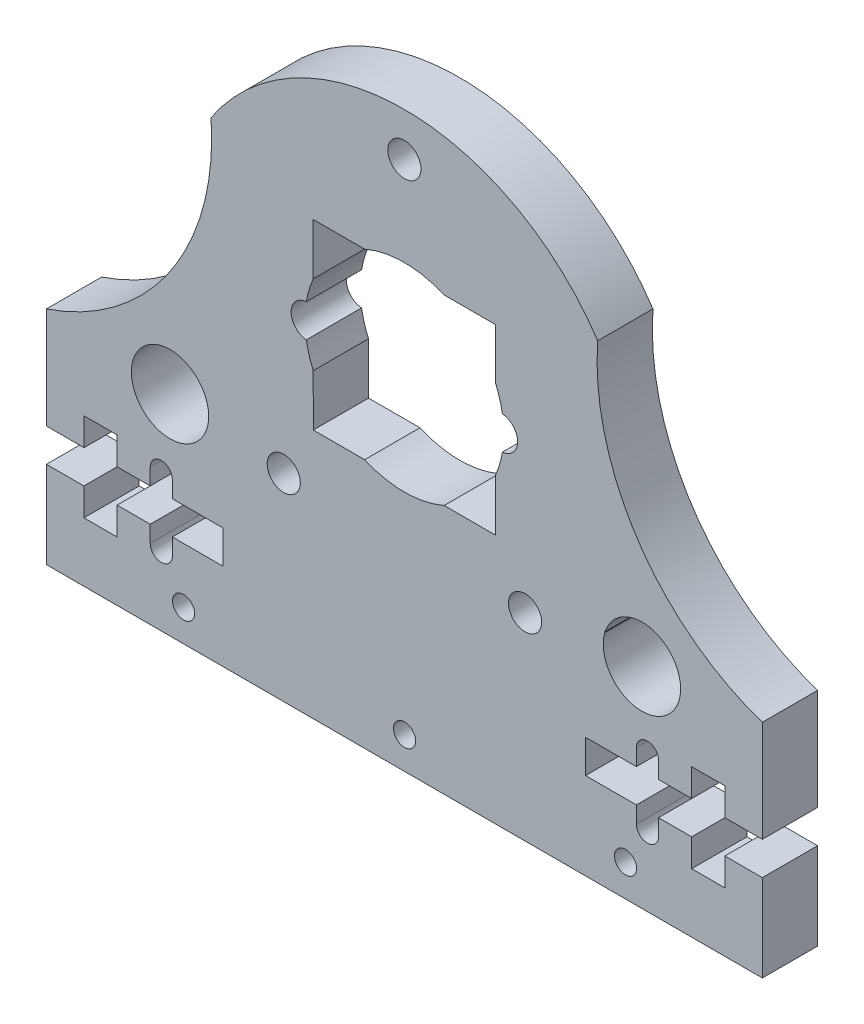
SolidWorks part; units mm, degrees
ref_plane "Front Plane" through (0, 0, 0) normal (0, 0, 1) x (1, 0, 0)
ref_plane "Top Plane" through (0, 0, 0) normal (0, 1, 0) x (1, 0, 0)
ref_plane "Right Plane" through (0, 0, 0) normal (1, 0, 0) x (0, 0, -1)
sketch "Sketch1" plane through (0, 0, 0) normal (0, 0, 1) x (1, 0, 0)
  line L0 (7.049, 19.6325) -> (17.9731, -10.4272)
  line L1 (-11.086, -20.4888) -> (10.9241, -20.4888)
  line L2 (-7.0493, 19.6315) -> (-17.9689, -10.4301)
  line L68 (-32.396, -10.8383) -> (-32.396, -30.8817)
  line L69 (-32.396, -10.8383) -> (32.396, -10.8383)
  line L70 (32.396, -10.8383) -> (32.396, -30.8817)
  line L71 (-32.396, -30.8817) -> (32.396, -30.8817)
  line L72 (-32.396, -10.8383) -> (32.396, -30.8817) construction
  line L73 (32.396, -10.8383) -> (-32.396, -30.8817) construction
  line L83 (8.2458, 8.2543) -> (3.5926, 8.2519)
  line L84 (-3.6012, 8.2481) -> (-8.2543, 8.2457)
  line L85 (-8.2543, 8.2457) -> (-8.2519, 3.5926)
  line L86 (-8.2481, -3.6012) -> (-8.2457, -8.2543)
  line L87 (-8.2457, -8.2543) -> (-3.5926, -8.2519)
  line L88 (3.6012, -8.2481) -> (8.2543, -8.2457)
  line L89 (8.2543, -8.2457) -> (8.2519, -3.5217)
  line L90 (8.2481, 3.672) -> (8.2458, 8.2543)
  arc A0 (7.049, 19.6325) -> (-7.0493, 19.6315) centre (0, 17.0709) ccw
  arc A1 (10.9241, -20.4888) -> (17.9731, -10.4272) centre (10.9241, -12.9888) ccw
  arc A2 (-17.9689, -10.4301) -> (-10.7531, -20.4888) centre (-10.9196, -12.9907) ccw
  circle A3 centre (0, 17.0709) radius 1.5
  circle A4 centre (10.9241, -12.9888) radius 1.5
  circle A5 centre (-10.9196, -12.9907) radius 1.5
  arc A6 (-28.1118, -10.8383) -> (-16.6025, -6.6683) centre (-21.209, -11.9221) cw
  arc A7 (16.6787, -6.8654) -> (28.4035, -10.8383) centre (21.5008, -11.9221) cw
  circle A8 centre (0, 0.0709) radius 17 construction
  circle A78 centre (21.5008, -11.9221) radius 3.5
  circle A79 centre (-21.209, -11.9221) radius 3.5
  arc A94 (3.5926, 8.2519) -> (-3.6012, 8.2481) centre (0, 0) ccw
  arc A95 (-8.2519, 3.5926) -> (-8.8758, 1.4902) centre (0, 0) ccw
  arc A96 (-8.8758, 1.4902) -> (-8.8742, -1.4994) centre (-8.75, -0.0045) ccw
  arc A97 (-8.8742, -1.4994) -> (-8.2481, -3.6012) centre (0, 0) ccw
  arc A98 (-3.5926, -8.2519) -> (3.6012, -8.2481) centre (0, 0) ccw
  arc A99 (8.2519, -3.5217) -> (8.8758, -1.4193) centre (0, 0.0709) ccw
  arc A100 (8.8758, -1.4193) -> (8.8742, 1.5702) centre (8.75, 0.0754) ccw
  arc A101 (8.8742, 1.5702) -> (8.2481, 3.672) centre (0, 0.0709) ccw
  point P18 (0, -20.86)
  dimension "D1" = 15
  dimension "D2" = 7
  dimension "D3" = 34
extrude "Boss-Extrude1" add sketch "Sketch1" along normal blind 5 contours A79 L69 A78 L0 A0 L2 A101 A100 A99 L89 L88 A98 L87 L86 A97 A96 A95 L85 L84 A94 L83 L90 A3 | A79 A2 L1 A1 A78 L69 A5 A4 | A79 L69 L68 L71 L70 A78 A1 L1 A2 | A79 L2 A6 L69 | A78 L69 A7 L0 region at (11.3885, 6.2108, 0) region at (22.5052, -7.7427, 0) region at (-0.0256, -23.2651, 0) region at (-22.3529, -7.7149, 0) region at (0.0494, -15.5713, 0)
sketch "Sketch2" plane through (0, 0, 5) normal (0, 0, 1) x (1, 0, 0)
  line L0 (26.0003, -21.5138) -> (24.396, -21.5138) construction
  line L1 (26.0003, -17.5138) -> (29.0003, -17.5138)
  line L2 (26.0003, -25.5138) -> (26.0003, -17.5138)
  line L3 (29.0003, -17.5138) -> (29.0003, -25.5138)
  line L4 (29.0003, -25.5138) -> (26.0003, -25.5138)
  line L5 (32.396, -23.0138) -> (16.396, -23.0138)
  line L6 (32.396, -23.0138) -> (32.396, -20.0138)
  line L7 (32.396, -20.0138) -> (16.396, -20.0138)
  line L8 (16.396, -23.0138) -> (16.396, -20.0138)
  line L9 (32.396, -23.0138) -> (16.396, -20.0138) construction
  line L10 (32.396, -20.0138) -> (16.396, -23.0138) construction
  line L11 (22.0003, -18.5138) -> (22.0003, -24.5138) construction
  line L12 (23.0003, -18.5138) -> (23.0003, -24.5138)
  line L13 (21.0003, -18.5138) -> (21.0003, -24.5138)
  line L14 (32.396, -10.8383) -> (32.396, -30.8817) construction
  arc A0 (23.0003, -18.5138) -> (21.0003, -18.5138) centre (22.0003, -18.5138) ccw
  arc A1 (21.0003, -24.5138) -> (23.0003, -24.5138) centre (22.0003, -24.5138) ccw
  point P4 (24.396, -21.5138)
  point P17 (22.0003, -21.5138)
  dimension "D1" = 3
  dimension "D2" = 16
  dimension "D3" = 2
  dimension "D4" = 8
  dimension "D5" = 3
  dimension "D6" = 8
extrude "Cut-Extrude3" cut sketch "Sketch2" against normal blind 10 contours L2 L1 L3 L4 | L5 L8 L7 L6 | A1 L12 A0 L13
mirror "Mirror1" about plane through (0, 0, 0) normal (1, 0, 0) of "Cut-Extrude3"
sketch "Sketch3" plane through (0, 0, 5) normal (0, 0, 1) x (1, 0, 0)
  line L0 (-7.0493, 19.6315) -> (-16.6025, -6.6683) construction
  line L1 (7.049, 19.6325) -> (16.6787, -6.8654) construction
  arc A0 (-9.7788, 12.1172) -> (9.7807, 12.1157) centre (0, 0) cw
  circle A1 centre (0, 17.0709) radius 1.5 construction
extrude "Cut-Extrude4" [suppressed] cut sketch "Sketch3" against normal through all and the other way through all
sketch "Sketch4" plane through (0, 0, 5) normal (0, 0, 1) x (1, 0, 0)
  line L0 (-32.396, -10.8383) -> (-17.4976, 11.6118)
  line L1 (32.396, -10.8383) -> (17.4976, 11.6118)
  line L4 (-32.396, -10.8383) -> (-32.396, -30.8817)
  line L5 (-32.396, -30.8817) -> (32.396, -30.8817)
  line L6 (32.396, -10.8383) -> (32.396, -30.8817)
  line L40 (-28.1118, -10.8383) -> (-32.396, -10.8383)
  line L41 (-7.0493, 19.6315) -> (-16.6025, -6.6683)
  line L42 (-28.1118, -10.8383) -> (-32.396, -10.8383)
  line L43 (-7.0493, 19.6315) -> (-16.6025, -6.6683)
  line L46 (-7.0493, 19.6315) -> (-6.984, 19.8046)
  line L47 (7.049, 19.6325) -> (6.984, 19.8046)
  line L48 (28.4035, -10.8383) -> (32.396, -10.8383)
  line L49 (7.049, 19.6325) -> (16.6787, -6.8654)
  line L50 (28.4035, -10.8383) -> (32.396, -10.8383)
  line L51 (7.049, 19.6325) -> (16.6787, -6.8654)
  arc A0 (17.4976, 11.6118) -> (-17.4976, 11.6118) centre (0, 0) ccw
  arc A18 (-16.6025, -6.6683) -> (-28.1118, -10.8383) centre (-21.209, -11.9221) ccw
  arc A19 (-16.6025, -6.6683) -> (-28.1118, -10.8383) centre (-21.209, -11.9221) ccw
  arc A21 (7.049, 19.6325) -> (-7.0493, 19.6315) centre (0, 17.0709) ccw construction
  arc A22 (28.4035, -10.8383) -> (16.6787, -6.8654) centre (21.5008, -11.9221) ccw
  arc A23 (28.4035, -10.8383) -> (16.6787, -6.8654) centre (21.5008, -11.9221) ccw
  dimension "D1" = 42
  dimension "D2" = 0
  dimension "D3" = 0
extrude "Cut-Extrude5" cut sketch "Sketch4" against normal blind 10 flip side to cut contours L4 L5 L6 L1 A0 L0 region at (0.0169, -11.9101, 5)
extrude "Boss-Extrude2" add sketch "Sketch4<5>" against normal blind 5 contours A19 L43 L46 A0 L0 L42 | A23 L50 L1 A0 L47 L51 region at (-18.1813, 3.5961, 5) region at (18.12, 3.66, 5)
sketch "Sketch4<5>" plane through (0, 0, 5) normal (0, 0, 1) x (1, 0, 0) same geometry as "Sketch4"
sketch "Sketch5" plane through (0, 0, 5) normal (0, 0, 1) x (1, 0, 0)
  circle A0 centre (0.0146, -28) radius 1
  circle A1 centre (0.0146, -28) radius 1 construction
  circle A2 centre (20.0146, -27.9896) radius 1
  circle A3 centre (-19.9854, -28.0104) radius 1
  circle A4 centre (-19.9854, -28.0104) radius 1 construction
  circle A5 centre (20.0146, -27.9896) radius 1 construction
  dimension "D1" = 2
extrude "Cut-Extrude6" cut sketch "Sketch5" against normal blind 5
sketch "Sketch6" plane through (0, 0, 5) normal (0, 0, 1) x (1, 0, 0)
  line L0 (32.396, -10.8383) -> (17.4976, 11.6118) construction
  arc A0 (-32.396, -10.8383) -> (-17.4976, 11.6118) centre (-39.4388, 10.0039) ccw
  arc A1 (32.396, -10.8383) -> (17.4976, 11.6118) centre (39.4388, 10.0039) cw
  arc A4 (17.4976, 11.6118) -> (-17.4976, 11.6118) centre (0, 0) ccw construction
  arc A5 (-17.4976, 11.6118) -> (-32.396, -10.8383) centre (-17.2079, -4.7489) ccw
  arc A6 (17.4976, 11.6118) -> (32.396, -10.8383) centre (17.2493, -4.7215) cw
  dimension "D1" = 22
extrude "Cut-Extrude7" cut sketch "Sketch6" against normal through all
